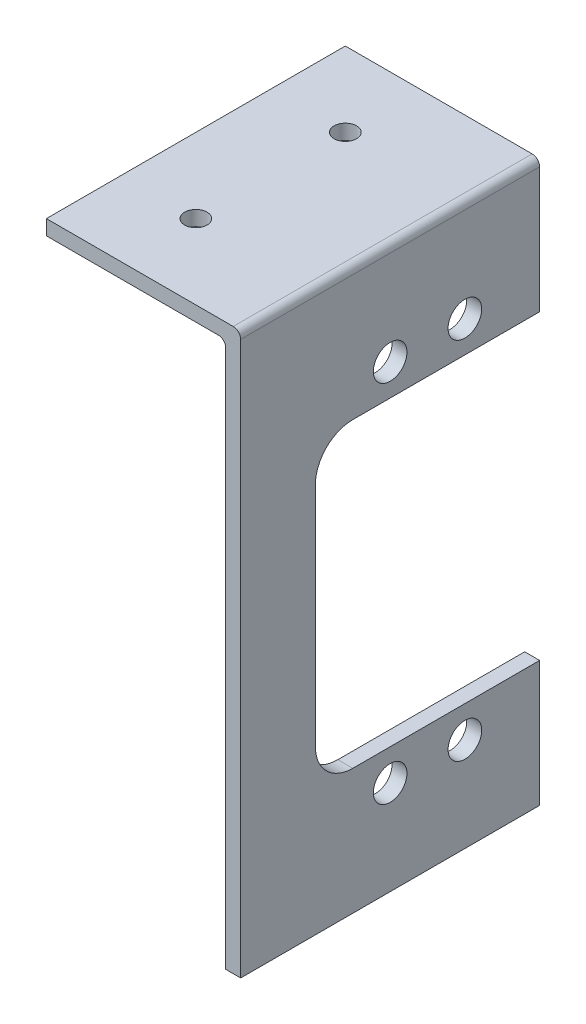
SolidWorks part; units mm, degrees
ref_plane "Front Plane" through (0, 0, 0) normal (0, 0, 1) x (1, 0, 0)
ref_plane "Top Plane" through (0, 0, 0) normal (0, 1, 0) x (1, 0, 0)
ref_plane "Right Plane" through (0, 0, 0) normal (1, 0, 0) x (0, 0, -1)
sketch "Sketch1" plane through (0, 0, 0) normal (0, 1, 0) x (1, 0, 0)
  line L1 (0, 0) -> (25, 0)
  line L2 (0, 0) -> (0, 40)
  line L3 (0, 40) -> (25, 40)
  line L4 (25, 0) -> (25, 40)
  circle A1 centre (10, 30) radius 1.5
  circle A2 centre (10, 10) radius 1.5
  dimension "D3" = 3
  dimension "D4" = 10
  dimension "D5" = 15
  dimension "D6" = 10
  dimension "D7" = 15
  dimension "D1" = 40
  dimension "D2" = 25
extrude "Boss-Extrude1" add sketch "Sketch1" along normal blind 2
sketch "Sketch2" plane through (0, 2, 0) normal (0, 1, 0) x (1, 0, 0)
  line L0 (0, 0) -> (25, 0) construction
  line L1 (25, 40) -> (24, 40)
  line L3 (25, 0) -> (24, 0)
  line L4 (24, 40) -> (24, 0)
  line L6 (25, 40) -> (26, 40)
  line L8 (25, 0) -> (26, 0)
  line L9 (26, 40) -> (26, 0)
  dimension "D1" = 1
  dimension "D2" = 1
extrude "Boss-Extrude2" add sketch "Sketch2" against normal blind 75
fillet "Fillet1" radius 1 2 edges at (24, 0, -20) (26, 2, -20)
sketch "Sketch3" plane through (24, 0, 0) normal (-1, 0, 0) x (0, 0, 1)
  line L0 (-25, -9) -> (-24.5, -9)
  line L1 (-25, -9) -> (-25, -15.8)
  line L2 (-25, -15.8) -> (-24.5, -15.8)
  line L3 (-24.5, -9) -> (-24.5, -15.8)
  line L4 (-25, -9) -> (-25.5, -9)
  line L5 (-25, -9) -> (-25, -15.8)
  line L6 (-25, -15.8) -> (-25.5, -15.8)
  line L7 (-25.5, -9) -> (-25.5, -15.8)
  line L8 (-25, -15.8) -> (-15, -15.8)
  line L9 (-25, -15.8) -> (-25, -56.2)
  line L10 (-25, -56.2) -> (-15, -56.2)
  line L11 (-15, -15.8) -> (-15, -56.2)
  line L12 (-25, -15.8) -> (-35, -15.8)
  line L13 (-25, -15.8) -> (-25, -56.2)
  line L14 (-25, -56.2) -> (-35, -56.2)
  line L15 (-35, -15.8) -> (-35, -56.2)
  line L16 (-25, -56.2) -> (-24.5, -56.2)
  line L17 (-25, -56.2) -> (-25, -63)
  line L18 (-25, -63) -> (-24.5, -63)
  line L19 (-24.5, -56.2) -> (-24.5, -63)
  line L20 (-25, -56.2) -> (-25.5, -56.2)
  line L21 (-25, -56.2) -> (-25, -63)
  line L22 (-25, -63) -> (-25.5, -63)
  line L23 (-25.5, -56.2) -> (-25.5, -63)
  line L24 (-40, -73) -> (0, -73) construction
  line L26 (0, -73) -> (0, -1) construction
  line L27 (-40, -73) -> (-40, 1) construction
  circle A0 centre (-30, -11.6) radius 2.25
  circle A1 centre (-20, -11.6) radius 2.25
  circle A2 centre (-20, -60.4) radius 2.25
  circle A3 centre (-30, -60.4) radius 2.25
  dimension "D19" = 10
  dimension "D1" = 0.5
  dimension "D2" = 0.5
  dimension "D3" = 6.8
  dimension "D4" = 40.4
  dimension "D5" = 10
  dimension "D6" = 10
  dimension "D7" = 4.5
  dimension "D8" = 4.2
  dimension "D9" = 4.5
  dimension "D10" = 4.2
  dimension "D11" = 0.5
  dimension "D12" = 0.5
  dimension "D13" = 6.8
  dimension "D14" = 4.2
  dimension "D15" = 4.5
  dimension "D16" = 4.5
  dimension "D17" = 4.2
  dimension "D18" = 10
  dimension "D20" = 15
extrude "Cut-Extrude1" cut sketch "Sketch3" against normal blind 75 contours A3 | L12 L15 L14 L9 L6 | A2 | L14 L23 L22 L17 | L19 L10 L17 L18 | L11 L8 L2 L9 L10 | A1 | A0 | L4 L7 L6 L1 | L3 L0 L1 L2 region at (24, -12.4, -24.75) region at (24, -12.4, -25.25) region at (24, -36, -30) region at (24, -36, -20) region at (24, -59.6, -25.25) region at (24, -59.6, -24.75) region at (24, -11.6, -30) region at (24, -11.6, -20) region at (24, -60.4, -20) region at (24, -60.4, -30)
sketch "Sketch4" plane through (26, 0, 0) normal (1, 0, 0) x (0, 0, -1)
  line L0 (40, -73) -> (40, 1) construction
  line L1 (40, -56.2) -> (10, -56.2)
  line L2 (40, -56.2) -> (40, -15.8)
  line L3 (40, -15.8) -> (10, -15.8)
  line L4 (10, -56.2) -> (10, -15.8)
  dimension "D1" = 30
  dimension "D2" = 40.4
extrude "Cut-Extrude2" cut sketch "Sketch4" against normal blind 10
sketch "Sketch5" plane through (26, 0, 0) normal (1, 0, 0) x (0, 0, -1)
  line L1 (25.5, -9) -> (24.5, -9)
  line L2 (25.5, -9) -> (25.5, -15.8)
  line L3 (25.5, -15.8) -> (24.5, -15.8)
  line L4 (24.5, -9) -> (24.5, -15.8)
  line L5 (25.5, -63) -> (24.5, -63)
  line L6 (25.5, -63) -> (25.5, -56.2)
  line L7 (25.5, -56.2) -> (24.5, -56.2)
  line L8 (24.5, -63) -> (24.5, -56.2)
extrude "Boss-Extrude3" add sketch "Sketch5" against normal blind 2
fillet "Fillet2" radius 5 2 edges at (25, -15.8, -10) (25, -56.2, -10)
